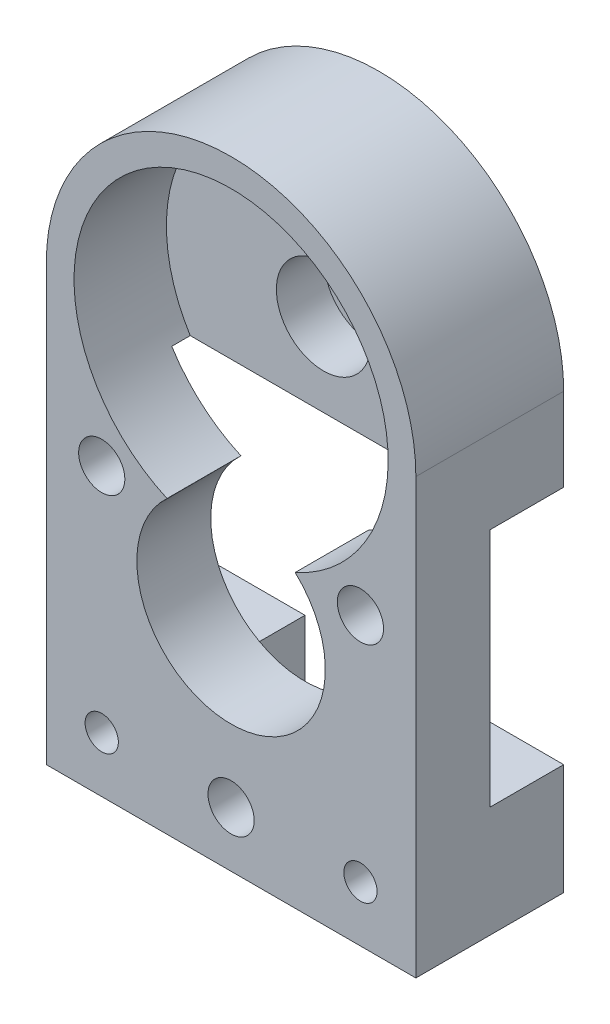
SolidWorks part; units mm, degrees
note: The reader was unsure of these and kept them because the rebuilt part matched: shared geometry of "草图2<4>", "草图1<5>", "草图6<3>", "草图6<4>".
ref_plane "前视基准面" through (0, 0, 0) normal (0, 0, 1) x (1, 0, 0)
ref_plane "上视基准面" through (0, 0, 0) normal (0, 1, 0) x (1, 0, 0)
ref_plane "右视基准面" through (0, 0, 0) normal (1, 0, 0) x (0, 0, -1)
other "Configuration Table"
sketch "草图1" plane through (0, 0, 0) normal (0, 0, 1) x (1, 0, 0)
  line L1 (-10, -6) -> (10, -6)
  line L2 (-10, -6) -> (-10, 6)
  line L3 (-10, 6) -> (10, 6)
  line L4 (10, -6) -> (10, 6)
  line L5 (-10, -6) -> (10, 6) construction
  line L6 (-10, 6) -> (10, -6) construction
  circle A8 centre (0, 0) radius 5.1
  circle A9 centre (-7, 3.5) radius 1.25
  circle A10 centre (-7, 3.5) radius 2
  circle A11 centre (7, 3.5) radius 1.25
  circle A12 centre (7, 3.5) radius 2
  circle A13 centre (0, 11.5) radius 8.5
  point P0 (0, 0)
  dimension "D1" = 7
  dimension "D2" = 11.5
  dimension "D3" = 17
  dimension "D5" = 10.2
  dimension "D8" = 2.5
  dimension "D9" = 4
  dimension "D4" = 8
  dimension "D6" = 20
  dimension "D7" = 12
  dimension "D10" = 7
extrude "凸台-拉伸1" add sketch "草图1" along normal mid plane 8 contours L3 A13 A8
sketch "草图2" plane through (0, 0, -4) normal (0, 0, -1) x (-1, 0, 0)
  line L0 (10, -6) -> (10, 6) construction
  line L1 (10, 11.5) -> (10, 6)
  line L2 (10, 6) -> (6.4807, 6) construction
  line L3 (-10, 6) -> (-10, 11.5)
  line L4 (-6.4807, 6) -> (-10, 6) construction
  line L5 (-10, 6) -> (10, 6)
  circle A0 centre (0, 11.5) radius 8.5
  arc A2 (3.4678, 3.7396) -> (6.4807, 6) centre (0, 11.5) ccw construction
  circle A3 centre (0, 11.5) radius 10
  line M5 (-6.4807, 6) -> (-10, 6)
  line M9 (10, 6) -> (6.4807, 6)
extrude "凸台-拉伸2" add sketch "草图2" against normal up to surface (8 mm away) contours A3 L3 L5 | A3 A0 L5 M5 | A3 L1 M9
extrude "凸台-拉伸3" add sketch "草图2<4>" against normal blind 3 contours L5 A0
sketch "草图2<4>" plane through (0, 0, -4) normal (0, 0, -1) x (-1, 0, 0) same geometry as "草图2"
extrude "切除-拉伸1" cut sketch "草图1<5>" along normal offset from surface (6 mm away) 2 from surface contours A10 | A12
sketch "草图1<5>" plane through (0, 0, 0) normal (0, 0, 1) x (1, 0, 0) same geometry as "草图1"
sketch "草图4" plane through (0, 0, -4) normal (0, 0, -1) x (-1, 0, 0)
  line L0 (10, -6) -> (10, 11.5) construction
  line L1 (10, 11.5) -> (-10, 11.5)
  line L2 (10, 11.5) -> (10, -6)
  line L3 (10, -6) -> (-10, -6)
  line L4 (-10, 11.5) -> (-10, -6)
  line L5 (10, -6) -> (-10, -6) construction
  line L6 (-10, -6) -> (-10, 11.5) construction
extrude "切除-拉伸2" cut sketch "草图4" against normal offset from surface (4 mm away) 2 up to face at (-5.75, 3.5, 2)
sketch "草图5" plane through (0, 0, 0) normal (0, 0, -1) x (-1, 0, 0)
  line L0 (10, -6) -> (10, 11.5) construction
  line L1 (10, -6) -> (-10, -6)
  line L2 (10, -6) -> (10, -12)
  line L3 (10, -12) -> (-10, -12)
  line L4 (-10, -6) -> (-10, -12)
  line L5 (-10, 11.5) -> (-10, -6) construction
  dimension "D1" = 6
extrude "凸台-拉伸4" add sketch "草图5" along normal up to surface and the other way up to surface
sketch "草图6" plane through (0, 0, -4) normal (0, 0, -1) x (-1, 0, 0)
  line L0 (-10, -6) -> (10, -6) construction
  line L1 (4, -6) -> (-4, -6)
  line L2 (4, -6) -> (4, -12)
  line L3 (4, -12) -> (-4, -12)
  line L4 (-4, -6) -> (-4, -12)
  line L5 (10, -12) -> (-10, -12) construction
  line L7 (10, -6) -> (10, -12) construction
  circle A0 centre (0, -9) radius 2
  circle A1 centre (0, -9) radius 1.25
  point P13 (0, -6)
  point P14 (4, -9)
  line M3 (10, -6) -> (-10, -6)
  line M5 (-10, -12) -> (10, -12)
  dimension "D1" = 4
  dimension "D2" = 2.5
  dimension "D3" = 6
extrude "切除-拉伸3" cut sketch "草图6" against normal up to surface (4 mm away) contours L4 L2 A0 M3 M5 | A0 A1 | A1
extrude "切除-拉伸4" cut sketch "草图6<3>" against normal through all contours A1
sketch "草图6<3>" plane through (0, 0, -4) normal (0, 0, -1) x (-1, 0, 0) same geometry as "草图6"
extrude "切除-拉伸5" cut sketch "草图6<4>" against normal up to surface (6 mm away) contours A0 up to face at (-5.75, 3.5, 2)
sketch "草图6<4>" plane through (0, 0, -4) normal (0, 0, -1) x (-1, 0, 0) same geometry as "草图6"
sketch "草图7" plane through (0, 0, -4) normal (0, 0, -1) x (-1, 0, 0)
  line L0 (10, -6) -> (10, -12) construction
  line L1 (10, -12) -> (4, -12) construction
  line L2 (-10, -12) -> (-10, -6) construction
  circle A0 centre (7, -9) radius 0.9
  circle A1 centre (-7, -9) radius 0.9
  circle A2 centre (0, 16) radius 0.9
  dimension "D3" = 1.8
  dimension "D1" = 3
  dimension "D2" = 3
  dimension "D4" = 3
  dimension "D5" = 16
extrude "切除-拉伸6" cut sketch "草图7" against normal through all
sketch "草图8" plane through (0, 0, 0) normal (0, 0, -1) x (-1, 0, 0)
  line L0 (10, 11.5) -> (-10, 11.5) construction
  line L1 (10, 11.5) -> (-10, 11.5)
  line L2 (10, 11.5) -> (10, 7)
  line L3 (10, 7) -> (-10, 7)
  line L4 (-10, 11.5) -> (-10, 7)
  line L5 (-10, 11.5) -> (-10, -6) construction
  arc A0 (10, 11.5) -> (-10, 11.5) centre (0, 11.5) ccw construction
  dimension "D1" = 4.5
extrude "凸台-拉伸5" add sketch "草图8" along normal up to surface (4 mm away) up to face at (-0.9, 16, -4)
sketch "草图9" plane through (0, 0, 0) normal (0, 0, 1) x (1, 0, 0)
  line L0 (-8.5, 11.5) -> (8.5, 11.5) construction
  circle A0 centre (0, 11.5) radius 8.5
  arc A1 (3.4678, 3.7396) -> (-3.4678, 3.7396) centre (0, 11.5) ccw construction
extrude "切除-拉伸7" cut sketch "草图9" against normal up to surface (1 mm away) up to face at (-0.9, 16, -1)
sketch "草图10" plane through (0, 0, -1) normal (0, 0, 1) x (1, 0, 0)
  circle A0 centre (0, 11.5) radius 2.55
  arc A1 (3.4678, 3.7396) -> (-3.4678, 3.7396) centre (0, 11.5) ccw construction
  dimension "D1" = 5.1
extrude "切除-拉伸8" cut sketch "草图10" against normal blind 2.6
